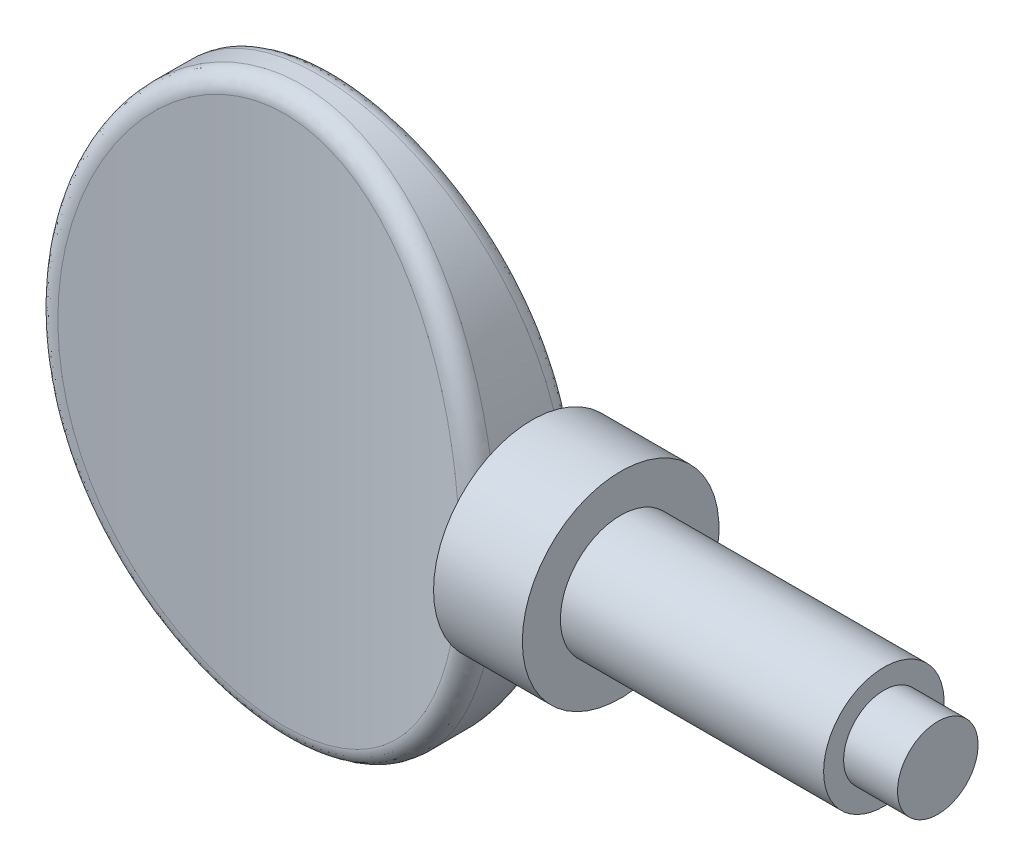
SolidWorks part; units mm, degrees
ref_plane "Front" through (0, 0, 0) normal (0, 0, 1) x (1, 0, 0)
ref_plane "Top" through (0, 0, 0) normal (0, 1, 0) x (1, 0, 0)
ref_plane "Right" through (0, 0, 0) normal (1, 0, 0) x (0, 0, -1)
ref_axis "Axis1" through (-50, 0, 0) along (1, 0, 0)
sketch "Sketch1" plane through (0, 0, 0) normal (0, 0, 1) x (1, 0, 0)
  line L0 (0, 0) -> (25.146, 0) construction
  line L1 (12.446, -3.937) -> (12.446, 3.937)
  ellipse E0 centre (0, 0) end of major axis (0, 11.303) minor radius 8.89
  dimension "D2" = 3.556
extrude "Extrude1" add sketch "Sketch1" along normal mid plane 4.572
sketch "Sketch2" plane through (0, 0, 0) normal (0, 1, 0) x (1, 0, 0)
  line L0 (8.89, 2.286) -> (-8.89, 2.286) construction
  line L1 (0, 0) -> (0, 1.1721) construction
  line L2 (-1.7991, 0) -> (2.0444, 0) construction
  line L3 (-8.89, -2.286) -> (8.89, -2.286) construction
  line L6 (-8.89, 2.286) -> (-8.89, -2.286)
  line L7 (8.89, 2.286) -> (8.89, -2.286)
  arc A0 (-8.89, 2.286) -> (8.89, 2.286) centre (0, 32.766) ccw
  arc A1 (-8.89, -2.286) -> (8.89, -2.286) centre (0, -32.766) cw
extrude "Cut-Extrude1" cut sketch "Sketch2" against normal through all and the other way through all flip side to cut
fillet "Fillet3" radius 0.6773 2 edges at (-8.875, -0.6558, 2.2816) (-1.5369, -11.1328, -1.0532)
sketch "Sketch3" plane through (0, 0, 0) normal (0, 1, 0) x (1, 0, 0)
  line L0 (12.446, 3.937) -> (12.446, 2.413)
  line L1 (0, 0) -> (21.0288, 0) construction
  line L2 (0, 0) -> (25.146, 0) construction
  line L3 (12.446, 2.413) -> (12.446, 0) construction
  line L4 (12.446, 2.413) -> (22.987, 2.413)
  line L5 (25.146, 0) -> (25.146, 1.6129)
  line L6 (12.446, 3.937) -> (8.89, 3.937)
  line L7 (7.2364, 1.8517) -> (7.2364, 0)
  line L8 (8.89, 0) -> (8.89, 3.937) construction
  line L9 (7.2364, 0) -> (25.146, 0)
  line L10 (25.146, 1.6129) -> (22.987, 1.6129)
  line L11 (22.987, 1.6129) -> (22.987, 2.413)
  arc A0 (8.89, 3.937) -> (7.2364, 1.8517) centre (6.7483, 3.937) cw
  arc A3 (-8.89, 2.286) -> (8.89, 2.286) centre (0, 32.766) ccw construction
  dimension "D1" = 7.874
revolve "Revolve1" add sketch "Sketch3" angle 360 about L0
cosmetic thread "Cosmetic Thread1" [suppressed]
sketch "Sketch4" plane through (0, 0, 0) normal (0, 0, 1) x (1, 0, 0)
  line L0 (0, 0) -> (27.7993, 0) construction
  line L1 (22.5881, 2.413) -> (22.987, 1.7221)
  line L2 (22.987, 1.7221) -> (23.3859, 2.413)
  line L3 (23.3859, 2.413) -> (23.3859, 3.2108)
  line L4 (23.3859, 3.2108) -> (22.5881, 3.2108)
  line L5 (22.5881, 3.2108) -> (22.5881, 2.413)
  line L6 (22.987, -2.413) -> (22.987, 2.413) construction
  dimension "D1" = 3.4442
  dimension "D2" = 4.826
revolve "Cut-Revolve10" [suppressed] cut sketch "Sketch4" angle 360 about L0
pattern_linear "LPattern10" [suppressed] count 10 along (-1, 0, 0) of bodies 109
equation "\"D2@Sketch1\" = \"B@Sketch1\" / 6"
equation "\"D1@Sketch3\" = \"E@Sketch1\""
equation "\"D1@Fillet3\" = \"C1@Sketch2\" / 3"
equation "\"D1@Sketch4\" = \"D2@Cosmetic Thread1\""
equation "\"D2@Sketch4\" = \"DIA@Sketch3\""
equation "\"D1@LPattern10\" =  ( \"L@Sketch1\" - \"Q@Sketch3\" )  / \"P@LPattern10\" "
